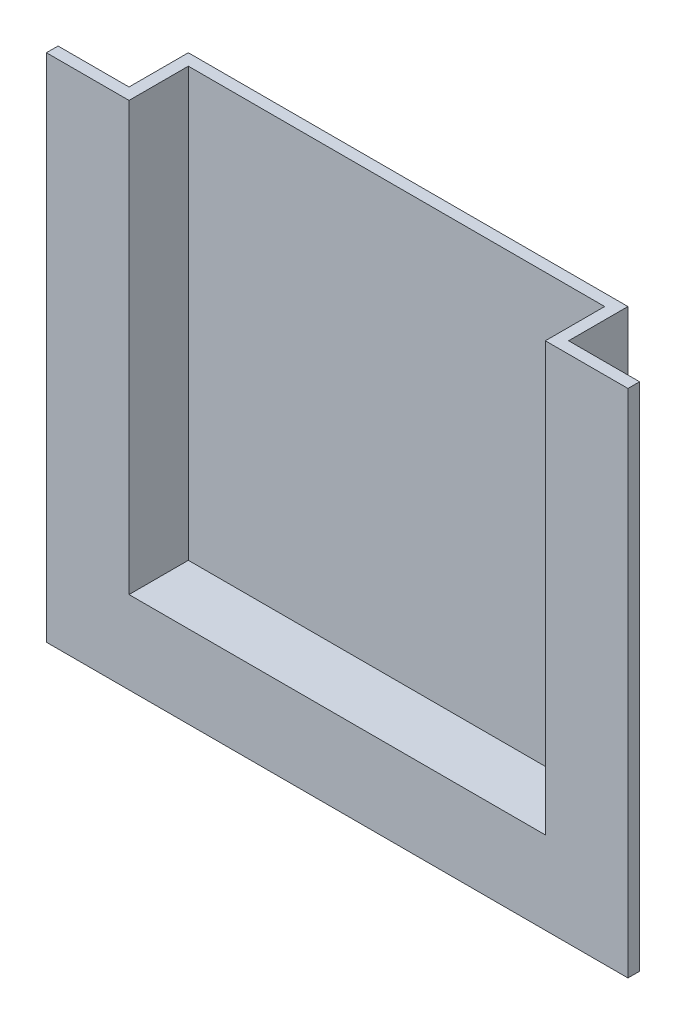
SolidWorks part; units mm, degrees
material "6063-O"
ref_plane "Front Plane" through (0, 0, 0) normal (0, 0, 1) x (1, 0, 0)
ref_plane "Top Plane" through (0, 0, 0) normal (0, 1, 0) x (1, 0, 0)
ref_plane "Right Plane" through (0, 0, 0) normal (1, 0, 0) x (0, 0, -1)
sketch "Sketch1" plane through (0, 0, 0) normal (0, 0, 1) x (1, 0, 0)
  line L1 (-48, -48) -> (48, -48)
  line L2 (-48, -48) -> (-48, 48)
  line L3 (-48, 48) -> (48, 48)
  line L4 (48, -48) -> (48, 48)
  line L5 (-48, -48) -> (48, 48) construction
  line L6 (-48, 48) -> (48, -48) construction
  point P0 (0, 0)
  dimension "D1" = 96
  dimension "D2" = 96
extrude "Boss-Extrude1" add sketch "Sketch1" along normal blind 15.494
sketch "Sketch2" plane through (0, 0, 15.494) normal (0, 0, 1) x (1, 0, 0)
  line L7 (-48, -48) -> (48, -48) construction
  line L9 (-63.5, 48) -> (-63.5, -63.5)
  line L10 (63.5, -63.5) -> (63.5, 48)
  line L11 (-63.5, -63.5) -> (63.5, -63.5)
  line L14 (-63.5, 48) -> (63.5, 48)
  line L15 (48, 48) -> (-48, 48) construction
  point P0 (0, -63.5)
  dimension "D1" = 127
  dimension "D2" = 15.5
extrude "Boss-Extrude2" add sketch "Sketch2" against normal blind 2.54
shell "Shell1" thickness 2.54 removed face at (0, -7.75, 15.494) removed face at (0, 48, 10.3505)
